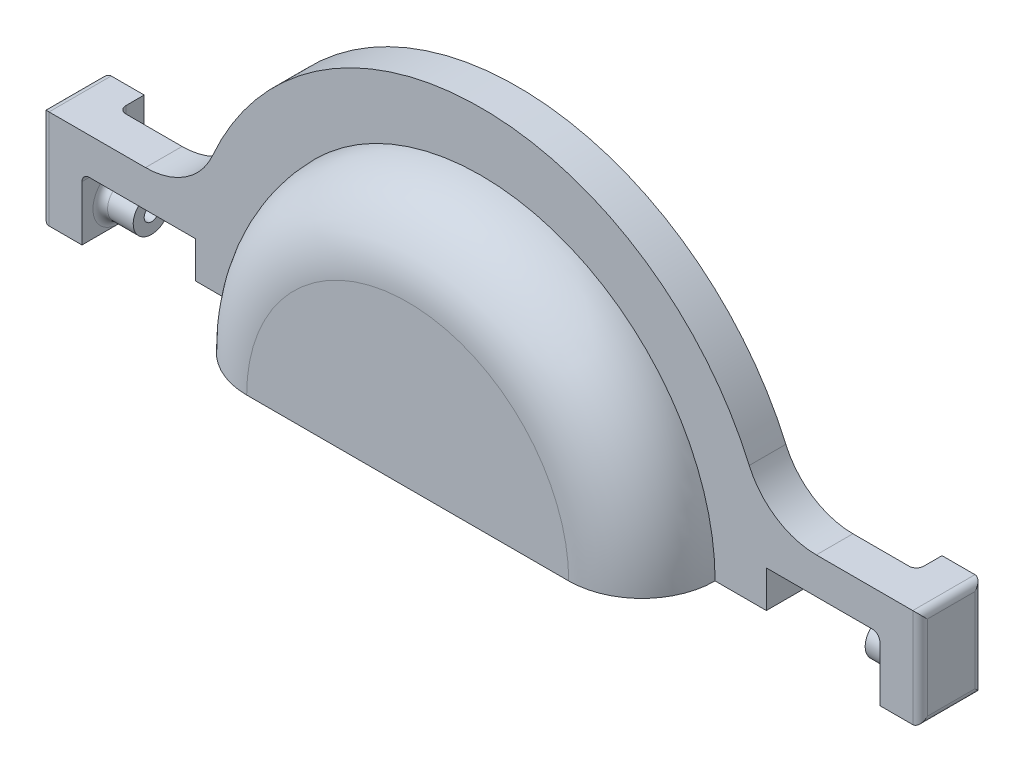
SolidWorks part; units mm, degrees
ref_plane "Front Plane" through (0, 0, 0) normal (0, 0, 1) x (1, 0, 0)
ref_plane "Top Plane" through (0, 0, 0) normal (0, 1, 0) x (1, 0, 0)
ref_plane "Right Plane" through (0, 0, 0) normal (1, 0, 0) x (0, 0, -1)
sketch "Sketch1" plane through (0, 0, 0) normal (0, 0, 1) x (1, 0, 0)
  circle A0 centre (0, 0) radius 32
extrude "Boss-Extrude1" add sketch "Sketch1" along normal blind 15 contours A0
fillet "Fillet1" radius 10 1 edges at (32, 0, 15)
shell "Shell1" thickness 2 removed face at (32, 0, 0)
sketch "Sketch2" plane through (0, 0, 0) normal (0, 0, -1) x (-1, 0, 0)
  line L0 (-55, -4.9501) -> (-40, -4.9501)
  line L1 (-60, 10) -> (-38.7298, 10)
  line L2 (-60, 10) -> (-60, -10)
  line L3 (-60, -10) -> (-38.7298, -10)
  line L4 (60, 10) -> (60, -10)
  line L7 (-55, -4.9501) -> (-55, 5.0499)
  line L8 (-40, -4.9501) -> (-40, 5.0499)
  line L9 (-55, 5.0499) -> (-40, 5.0499)
  line L10 (-55, -4.9501) -> (-40, 5.0499) construction
  line L11 (-40, -4.9501) -> (-55, 5.0499) construction
  line L12 (55, -5) -> (40, -5)
  line L13 (55, -5) -> (55, 5)
  line L14 (40, -5) -> (40, 5)
  line L15 (55, 5) -> (40, 5)
  line L16 (55, -5) -> (40, 5) construction
  line L17 (40, -5) -> (55, 5) construction
  line L18 (38.7298, 10) -> (60, 10)
  line L21 (38.7298, -10) -> (60, -10)
  arc A0 (38.7298, 10) -> (-38.7298, 10) centre (0, 0) ccw
  arc A1 (-38.7298, -10) -> (38.7298, -10) centre (0, 0) ccw
  point P8 (-47.5, 0.0499)
  point P9 (47.5, 0)
  dimension "D1" = 120
  dimension "D2" = 20
  dimension "D3" = 15
  dimension "D4" = 15
  dimension "D5" = 10
  dimension "D6" = 10
  dimension "D7" = 40
  dimension "D8" = 5
  dimension "D9" = 40
extrude "Boss-Extrude2" add sketch "Sketch2" against normal blind 5 contours L1 A0 L18 L4 L21 A1 L3 L2 | L9 L8 L0 L7 | L15 L14 L12 L13
sketch "Sketch3" plane through (0, 0, 0) normal (0, 0, -1) x (-1, 0, 0)
  circle A0 centre (0, 0) radius 29
extrude "Cut-Extrude1" cut sketch "Sketch3" against normal blind 5 contours A0
sketch "Sketch4" plane through (0, 0, 0) normal (0, 0, -1) x (-1, 0, 0)
  line L0 (-60, 0) -> (60, 0)
  line L1 (-60, 10) -> (-60, -10) construction
  line L2 (60, 10) -> (60, -10) construction
split "Split1" trim tools "Sketch4" bodies to split 103 resulting bodies 104 105
delete or keep bodies "Body-Delete1" type delete bodies bodies 104
sketch "Sketch5" plane through (-55, 0, 0) normal (1, 0, 0) x (0, 0, -1)
  circle A0 centre (0, 0) radius 1
  circle A1 centre (0, 0) radius 2.5
sketch "Sketch6" plane through (55, 0, 0) normal (-1, 0, 0) x (0, 0, 1)
  circle A0 centre (0, 0) radius 1
  circle A1 centre (0, 0) radius 2.5
extrude "Boss-Extrude3" add sketch "Sketch6" along normal blind 5 contours A0 | A1
extrude "Boss-Extrude4" add sketch "Sketch5" along normal blind 5 contours A1 | A0
sketch "Sketch7" plane through (60, 0, 0) normal (1, 0, 0) x (0, 0, -1)
  line L0 (-5, 10) -> (-5, 0) construction
  line L1 (-5, 10) -> (3.5, 10)
  line L2 (-5, 10) -> (-5, -3.5)
  line L3 (-5, -3.5) -> (3.5, -3.5)
  line L4 (3.5, 10) -> (3.5, -3.5)
  line L5 (-5, 32) -> (-5, 0) construction
  dimension "D1" = 3.5
  dimension "D2" = 3.5
sketch "Sketch8" plane through (-60, 0, 0) normal (-1, 0, 0) x (0, 0, 1)
  line L1 (5, 10) -> (-3.5, 10)
  line L2 (5, 10) -> (5, -3.5)
  line L3 (5, -3.5) -> (-3.5, -3.5)
  line L4 (-3.5, 10) -> (-3.5, -3.5)
extrude "Boss-Extrude5" add sketch "Sketch7" against normal blind 5.5 contours L4 L3 L2 L1
extrude "Boss-Extrude6" add sketch "Sketch8" against normal blind 5.5 contours L4 L3 L2 L1
fillet "Fillet2" [suppressed] radius 1
fillet "Fillet3" radius 1 14 edges at (-60, 3.25, -3.5) (-60, 10, 0.75) (-60, 3.25, 5) (-60, -3.5, 0.75) (60, 10, 0.75) (60, 3.25, -3.5) (60, -3.5, 0.75) (60, 3.25, 5) (-54.5, 5, 2.5) (54.5, 5.0499, 2.5) (54.5, 7.525, 0) (-54.5, 7.5, 0) (-54.5, -2.5, 0) (54.5, 0, 2.5)
fillet "Fillet4" radius 10 2 edges at (-38.7298, 10, 2.5) (38.7298, 10, 2.5)
sketch "Sketch9" plane through (0, 0, 0) normal (0, 0, -1) x (-1, 0, 0)
  line L0 (-60, 0) -> (60, 0) construction
  line L1 (-40, 5.0499) -> (-39, 5.0499)
  line L2 (-40, 5.0499) -> (-40, 0)
  line L3 (-40, 0) -> (-39, 0)
  line L4 (-39, 5.0499) -> (-39, 0)
  line L6 (40, 5) -> (39, 5)
  line L7 (40, 5) -> (40, 0)
  line L8 (40, 0) -> (39, 0)
  line L9 (39, 5) -> (39, 0)
  dimension "D1" = 1
  dimension "D2" = 1
extrude "Cut-Extrude2" cut sketch "Sketch9" against normal blind 10 contours L4 L3 L2 L1 | L9 L8 L7 L6
